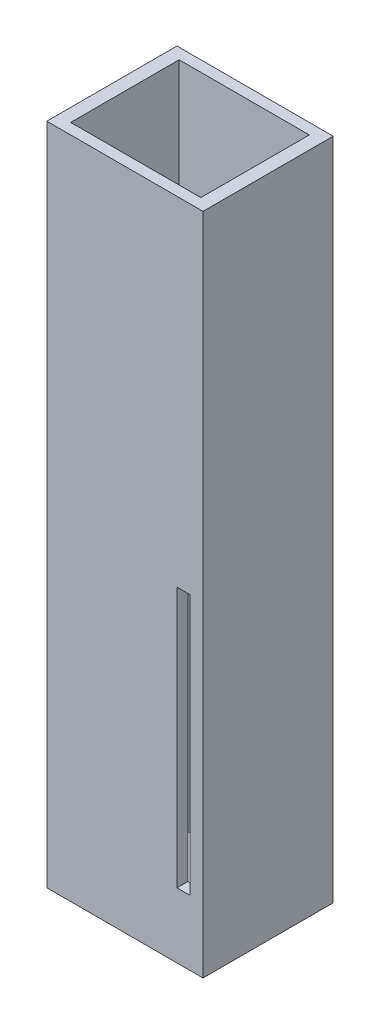
SolidWorks part; units mm, degrees
ref_plane "Front Plane" through (0, 0, 0) normal (0, 0, 1) x (1, 0, 0)
ref_plane "Top Plane" through (0, 0, 0) normal (0, 1, 0) x (1, 0, 0)
ref_plane "Right Plane" through (0, 0, 0) normal (1, 0, 0) x (0, 0, -1)
sketch "Sketch1" plane through (0, 0, 0) normal (0, 1, 0) x (1, 0, 0)
  line L1 (-3, -2.5) -> (3, -2.5)
  line L2 (-3, -2.5) -> (-3, 2.5)
  line L3 (-3, 2.5) -> (3, 2.5)
  line L4 (3, -2.5) -> (3, 2.5)
  line L5 (-3, -2.5) -> (3, 2.5) construction
  line L6 (-3, 2.5) -> (3, -2.5) construction
  line L7 (-2.5, -2.0833) -> (2.5, -2.0833)
  line L8 (-2.5, -2.0833) -> (-2.5, 2.0833)
  line L9 (-2.5, 2.0833) -> (2.5, 2.0833)
  line L10 (2.5, -2.0833) -> (2.5, 2.0833)
  line L11 (-2.5, -2.0833) -> (2.5, 2.0833) construction
  line L12 (-2.5, 2.0833) -> (2.5, -2.0833) construction
  point P0 (0, 0)
  point P6 (0, 0)
  dimension "D1" = 5
  dimension "D2" = 6
  dimension "D3" = 5
extrude "Boss-Extrude1" add sketch "Sketch1" along normal blind 25.5
sketch "Sketch2" plane through (0, 0, 2.5) normal (0, 0, 1) x (1, 0, 0)
  line L0 (-3, 0) -> (3, 0) construction
  line L1 (2, 2.5) -> (2.5, 2.5)
  line L2 (2, 2.5) -> (2, 12.5)
  line L3 (2, 12.5) -> (2.5, 12.5)
  line L4 (2.5, 2.5) -> (2.5, 12.5)
  line L5 (3, 25.5) -> (3, 0) construction
  dimension "D1" = 0.5
  dimension "D2" = 10
  dimension "D3" = 2.5
  dimension "D4" = 0.5
extrude "Cut-Extrude1" cut sketch "Sketch2" against normal through all both and the other way through all
scale "Scale1" scale about centroid uniform scaling yes scale factor 6
